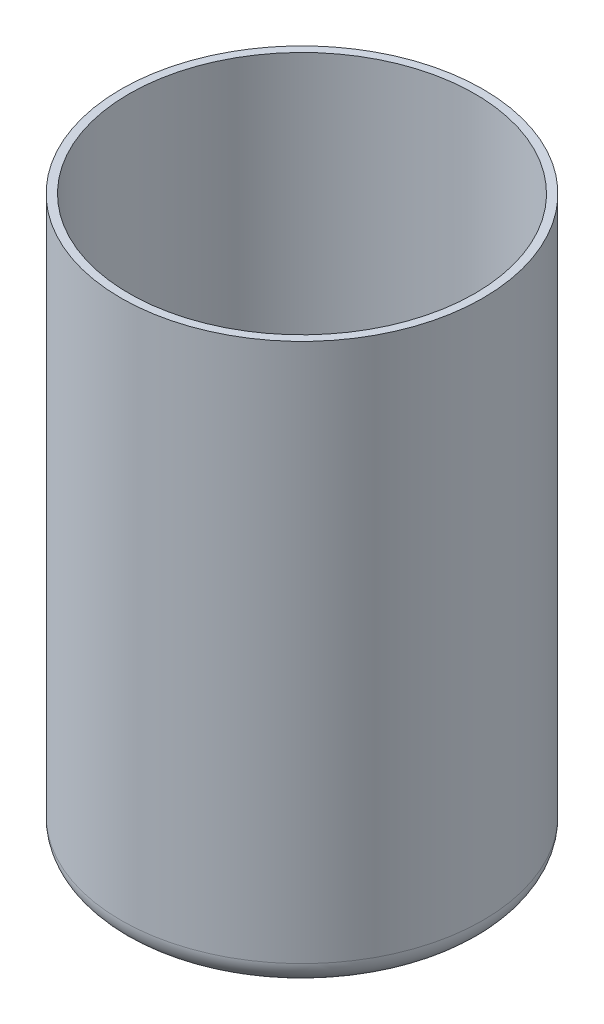
SolidWorks part; units mm, degrees
note: The reader was unsure of these and kept them because the rebuilt part matched: shared geometry of "Sketch1<3>".
material "Glass"
ref_plane "Front Plane" through (0, 0, 0) normal (0, 0, 1) x (1, 0, 0)
ref_plane "Top Plane" through (0, 0, 0) normal (0, 1, 0) x (1, 0, 0)
ref_plane "Right Plane" through (0, 0, 0) normal (1, 0, 0) x (0, 0, -1)
sketch "Sketch1" plane through (0, 0, 0) normal (0, 1, 0) x (1, 0, 0)
  circle A0 centre (0, 0) radius 21.5
  circle A1 centre (0, 0) radius 22.5
  dimension "D1" = 45
  dimension "D2" = 43
extrude "Extrude-Thin1" add sketch "Sketch1" along normal blind 70 thin contours A0 | A1 A0
extrude "Boss-Extrude1" add sketch "Sketch1<3>" along normal blind 1 contours A0
sketch "Sketch1<3>" plane through (0, 0, 0) normal (0, 1, 0) x (1, 0, 0) same geometry as "Sketch1"
fillet "Fillet1" radius 3 1 edges at (0, 0, 22.5)
sketch "Sketch2" plane through (0, 0, 0) normal (0, -1, 0) x (1, 0, 0)
  circle A0 centre (0, 0) radius 1.5
  dimension "D1" = 3
extrude "Cut-Extrude1" cut sketch "Sketch2" against normal blind 1
